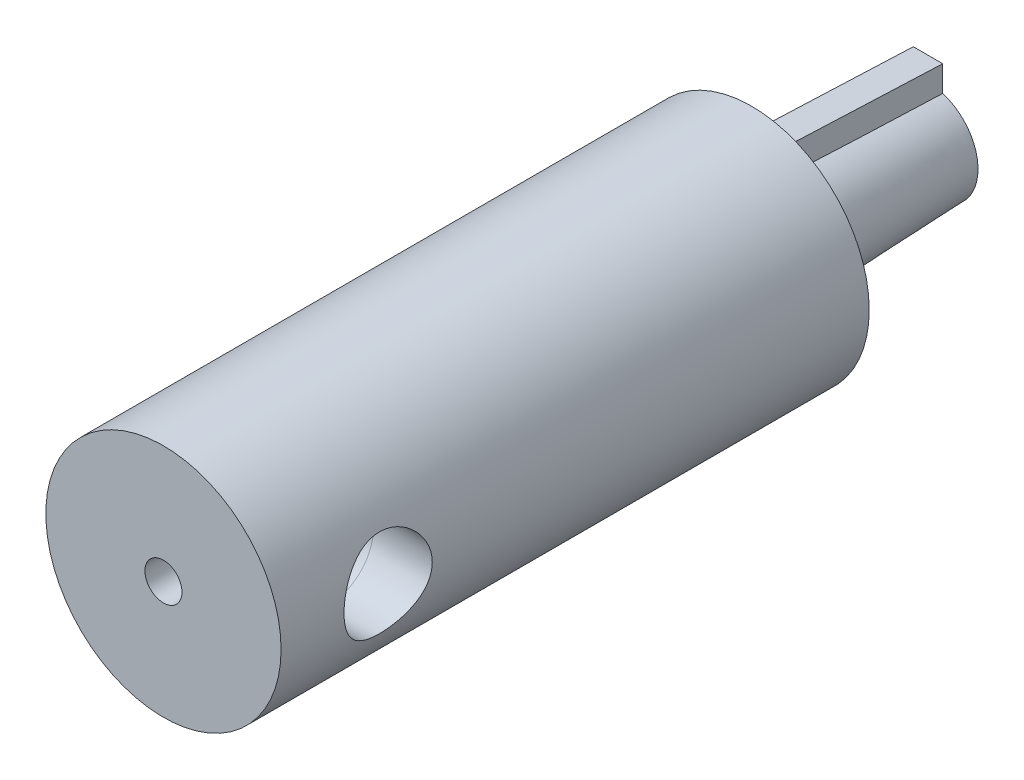
SolidWorks part; units mm, degrees
ref_plane "Front Plane" through (0, 0, 0) normal (0, 0, 1) x (1, 0, 0)
ref_plane "Top Plane" through (0, 0, 0) normal (0, 1, 0) x (1, 0, 0)
ref_plane "Right Plane" through (0, 0, 0) normal (1, 0, 0) x (0, 0, -1)
sketch "Sketch1" plane through (0, 0, 0) normal (0, 0, 1) x (1, 0, 0)
  circle A0 centre (0, 0) radius 20
  dimension "D1" = 40
extrude "Boss-Extrude1" add sketch "Sketch1" along normal blind 100
sketch "Sketch2" plane through (0, 0, 0) normal (0, 0, -1) x (-1, 0, 0)
  circle A0 centre (0, 0) radius 7.5
  dimension "D1" = 15
sketch "Sketch3" plane through (0, 0, 100) normal (0, 0, 1) x (1, 0, 0)
  circle A0 centre (0, 0) radius 3.15
  dimension "D1" = 6.3
extrude "Cut-Extrude2" cut sketch "Sketch3" against normal blind 5
sketch "Sketch4" plane through (0, 0, 0) normal (0, 1, 0) x (1, 0, 0)
  line L0 (0, 0) -> (0, -71.7939)
  line L1 (10, -81.7939) -> (20, -81.7939)
  line L3 (20, -100) -> (20, 0) construction
  arc A0 (0, -71.7939) -> (10, -81.7939) centre (10, -71.7939) ccw
  dimension "D1" = 10
sweep "Cut-Sweep1" cut profiles "Sketch2" path "Sketch4"
sketch "Sketch5" plane through (0, 0, 0) normal (0, 0, -1) x (-1, 0, 0)
  circle A0 centre (0, 0) radius 9.75
  dimension "D1" = 19.5
ref_plane "Plane1" through (0, 0, -30) normal (0, 0, 1) x (1, 0, 0)
sketch "Sketch6" plane through (0, 0, -30) normal (0, 0, 1) x (1, 0, 0)
  circle A0 centre (0, 0) radius 8.5
  dimension "D1" = 17
loft "Loft1" add profiles "Sketch6", "Sketch5" connector at (3.3021, -7.8324, -30) connector at (5.6763, -7.9273, 0)
sketch "Sketch7" plane through (0, 0, -30) normal (0, 0, -1) x (-1, 0, 0)
  circle A0 centre (0, 0) radius 4
  dimension "D1" = 8
extrude "Cut-Extrude3" cut sketch "Sketch7" against normal blind 30 contours A0
sketch "Sketch8" plane through (0, 0, -30) normal (0, 0, 1) x (1, 0, 0)
  line L0 (0, 0.7875) -> (0, 0) construction
  line L1 (0, 0) -> (0, 15.5007) construction
  line L2 (0, 0) -> (-21.2128, -12.2472) construction
  dimension "D1" = 120
sketch "Sketch9" plane through (0, 0, -30) normal (0, 0, 1) x (1, 0, 0)
  line L0 (0, 0) -> (0, 15.5007) construction
  line L1 (2.5, 5.7642) -> (-2.5, 5.7642)
  line L2 (2.5, 5.7642) -> (2.5, 12.5)
  line L3 (2.5, 12.5) -> (-2.5, 12.5)
  line L4 (-2.5, 5.7642) -> (-2.5, 12.5)
  line L5 (0, 8.5) -> (23.3832, 8.5) construction
  line L6 (23.3832, 8.5) -> (-17.3304, 8.5) construction
  circle A0 centre (0, 0) radius 8.5 construction
  dimension "D1" = 2.5
  dimension "D2" = 5
  dimension "D3" = 4
sketch "Sketch12" plane through (0, 0, 0) normal (0, 0, -1) x (-1, 0, 0)
  line L0 (0, 0) -> (0, 23.8516) construction
  line L1 (0, 9.75) -> (-17.4625, 9.75) construction
  line L2 (-17.4625, 9.75) -> (17.4625, 9.75) construction
  line L3 (2.5, 5.7642) -> (2.5, 12.5) construction
  line L4 (-2.5, 13.75) -> (2.5, 13.75)
  line L5 (-2.5, 13.75) -> (-2.5, 6.7704)
  line L6 (-2.5, 6.7704) -> (2.5, 6.7704)
  line L7 (2.5, 13.75) -> (2.5, 6.7704)
  circle A0 centre (0, 0) radius 9.75 construction
  circle A1 centre (0, 0) radius 20 construction
  dimension "D1" = 4
  dimension "D2" = 2.5
  dimension "D3" = 5
loft "Loft2" add profiles "Sketch12", "Sketch9" connector at (2.5, 13.75, 0) connector at (2.5, 12.5, -30)
pattern_circular "CirPattern1" count 2 every 240 about axis through (0, 0, 0) along (0, 0, -1) of "Loft2"
